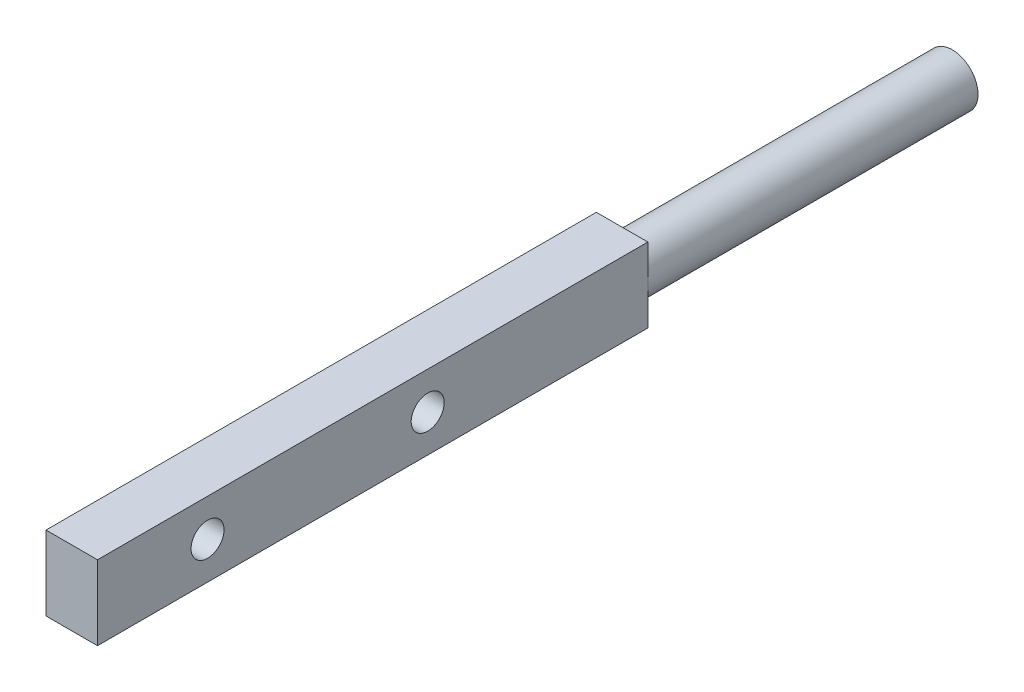
SolidWorks part; units mm, degrees
ref_plane "Front Plane" through (0, 0, 0) normal (0, 0, 1) x (1, 0, 0)
ref_plane "Top Plane" through (0, 0, 0) normal (0, 1, 0) x (1, 0, 0)
ref_plane "Right Plane" through (0, 0, 0) normal (1, 0, 0) x (0, 0, -1)
sketch "Sketch1" plane through (0, 0, 0) normal (0, 0, 1) x (1, 0, 0)
  line L1 (0, 0) -> (4.6777, 0)
  line L2 (0, 0) -> (0, 6.7646)
  line L3 (0, 6.7646) -> (4.6777, 6.7646)
  line L4 (4.6777, 0) -> (4.6777, 6.7646)
  dimension "D1" = 4.6777
  dimension "D2" = 6.7646
extrude "Boss-Extrude1" add sketch "Sketch1" along normal blind 50
sketch "Sketch2" plane through (0, 0, 0) normal (0, 0, -1) x (-1, 0, 0)
  line L0 (-2.3388, 0) -> (-2.3388, 6.7646) construction
  line L1 (0, 0) -> (-4.6777, 0) construction
  line L2 (-4.6777, 6.7646) -> (0, 6.7646) construction
  line L5 (-4.6777, 0) -> (-4.6777, 6.7646) construction
  circle A0 centre (-2.3388, 3.3823) radius 2.3388
  point P9 (-2.3388, 3.3823)
extrude "Boss-Extrude2" add sketch "Sketch2" along normal blind 30
ref_plane "Plane4" through (2.3388, 0, 0) normal (-1, 0, 0) x (0, 0, 1)
sketch "Sketch3" plane through (4.6777, 0, 0) normal (1, 0, 0) x (0, 0, -1)
  line L0 (0, 3.3823) -> (-20, 3.3823) construction
  line L2 (-20, 3.3823) -> (-40, 3.3823) construction
  circle A0 centre (-20, 3.3823) radius 1.5
  circle A1 centre (-40, 3.3823) radius 1.5
  dimension "D1" = 3
  dimension "D2" = 3
  dimension "D3" = 20
  dimension "D4" = 20
extrude "Cut-Extrude1" cut sketch "Sketch3" against normal through all
equation "\"D1@Boss-Extrude1\"= \"LA_length\""
equation "\"LA_width\"=4.67766733"
equation "\"LA_height\"=6.76462661"
equation "\"D1@Sketch1\"=\"LA_width\""
equation "\"D2@Sketch1\"=\"LA_height\""
equation "\"LA_length\"=50.00000000"
equation "\"radius_pin\"=2.33883367"
